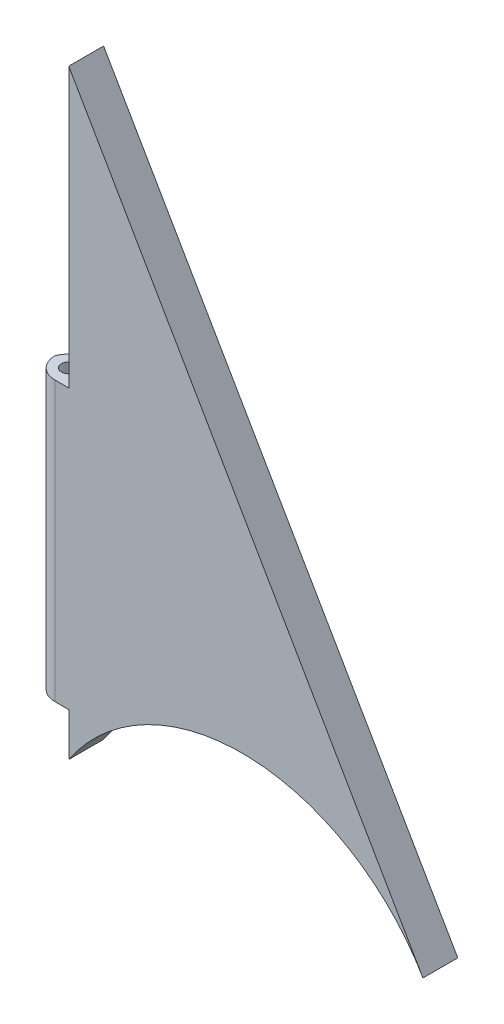
SolidWorks part; units mm, degrees
ref_plane "Plan de face" through (0, 0, 0) normal (0, 0, 1) x (1, 0, 0)
ref_plane "Plan de dessus" through (0, 0, 0) normal (0, 1, 0) x (1, 0, 0)
ref_plane "Plan de droite" through (0, 0, 0) normal (1, 0, 0) x (0, 0, -1)
sketch "Esquisse1" plane through (0, 0, 0) normal (0, 0, 1) x (1, 0, 0)
  line L0 (26.025, -0.448) -> (-24.8298, 87.5088)
  line L1 (-24.8298, 87.5088) -> (-24.8298, 1.2934)
  arc A0 (26.025, -0.448) -> (-24.8298, 1.2934) centre (0.0536, -15.4641) ccw
  dimension "D1" = 30
extrude "Boss.-Extru.1" add sketch "Esquisse1" along normal blind 5 contours L1 A0 L0
ref_plane "Plan3" through (0, 47.4899, 0) normal (0, 1, 0) x (1, 0, 0)
sketch "Esquisse9" plane through (0, 47.4899, 0) normal (0, 1, 0) x (1, 0, 0)
  line L0 (-24.8298, -5) -> (-24.8298, 0)
  line L1 (-24.8298, -5) -> (-29.8298, -5)
  line L2 (-24.8298, 0) -> (-29.8298, 0)
  line L3 (-29.8298, -5) -> (-29.8298, 0)
  dimension "D1" = 5
  dimension "D2" = 5
extrude "Boss.-Extru.3" add sketch "Esquisse9" against normal blind 40
sketch "Esquisse10" plane through (0, 47.4899, 0) normal (0, 1, 0) x (1, 0, 0)
sketch "Esquisse12" plane through (0, 47.4899, 0) normal (0, 1, 0) x (1, 0, 0)
  circle A1 centre (-27.3298, -2.5) radius 1.0488
extrude "Enlèv. mat.-Extru.3" cut sketch "Esquisse12" against normal blind 40
fillet "Congé3" radius 3 1 edges at (-29.8298, 27.4899, 5)
fillet "Congé4" radius 3 1 edges at (-29.8298, 27.4899, 0)
